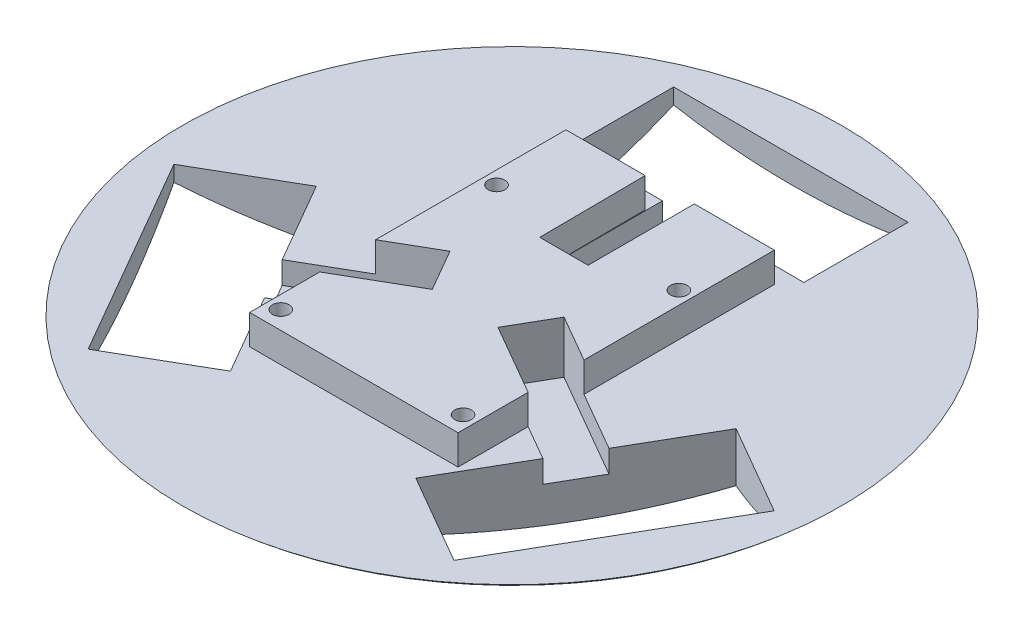
SolidWorks part; units mm, degrees
ref_plane "Front Plane" through (0, 0, 0) normal (0, 0, 1) x (1, 0, 0)
ref_plane "Top Plane" through (0, 0, 0) normal (0, 1, 0) x (1, 0, 0)
ref_plane "Right Plane" through (0, 0, 0) normal (1, 0, 0) x (0, 0, -1)
sketch "Sketch2" plane through (0, 0, 0) normal (0, 1, 0) x (1, 0, 0)
  line L0 (0, -68.0098) -> (0, 65.7503) construction
  line L1 (-31.5, 74.9495) -> (31.5, 74.9495)
  line L2 (-31.5, 74.9495) -> (-31.5, 46.9495)
  line L3 (-31.5, 46.9495) -> (31.5, 46.9495)
  line L4 (31.5, 74.9495) -> (31.5, 46.9495)
  line L5 (-31.5, 74.9495) -> (31.5, 46.9495) construction
  line L6 (-31.5, 46.9495) -> (31.5, 74.9495) construction
  line L7 (-70.2148, 0) -> (95.7201, 0) construction
  line L8 (0, 0) -> (-72.5813, -41.9048) construction
  line L9 (0, 0) -> (72.5813, -41.9048) construction
  line L10 (80.6581, -10.1949) -> (49.1581, -64.7545)
  line L11 (56.4094, 3.8051) -> (24.9094, -50.7545)
  line L12 (80.6581, -10.1949) -> (56.4094, 3.8051)
  line L13 (49.1581, -64.7545) -> (24.9094, -50.7545)
  line L14 (-49.1581, -64.7545) -> (-80.6581, -10.1949)
  line L15 (-24.9094, -50.7545) -> (-56.4094, 3.8051)
  line L16 (-49.1581, -64.7545) -> (-24.9094, -50.7545)
  line L17 (-80.6581, -10.1949) -> (-56.4094, 3.8051)
  line L18 (-6.5, -8.0505) -> (6.5, 46.9495) construction
  line L19 (-6.5, 46.9495) -> (6.5, 46.9495)
  line L20 (-6.5, 46.9495) -> (-6.5, -8.0505)
  line L21 (-6.5, -8.0505) -> (6.5, -8.0505)
  line L22 (6.5, 46.9495) -> (6.5, -8.0505)
  line L23 (-6.5, 46.9495) -> (6.5, -8.0505) construction
  line L24 (31.4023, -15.1408) -> (6.5, -0.7634)
  line L25 (-6.1216, -8.0505) -> (0, 2.5524)
  line L26 (24.9023, -26.3991) -> (0, -12.0218)
  line L27 (-25.0514, -26.4852) -> (0, -12.0218)
  line L28 (0, 2.5524) -> (6.1216, -8.0505)
  line L29 (-33.4324, -16.3129) -> (-6.5, -0.7634)
  circle A2 centre (0, 0) radius 16 construction
  point P3 (0, 19.4495)
  point P4 (0, 46.9495)
  point P6 (0, 60.9495)
  point P13 (0, 0)
  point P33 (0, 0)
  point P41 (0, -4.5162)
  dimension "D1" = 55
  dimension "D2" = 13
  dimension "D3" = 32
  dimension "D5" = 63
  dimension "D6" = 120
  dimension "D7" = 28
  dimension "D8" = 3
  dimension "D4" = 3
sketch "Sketch3" plane through (0, 0, 0) normal (1, 0, 0) x (0, 0, -1)
  line L0 (0, 83.7838) -> (0, -101.0811) construction
  line L1 (-115.9459, 0) -> (127.2973, 0) construction
  line L5 (0, 20) -> (0, 0)
  line L6 (88.569, 20) -> (0, 20)
  arc A3 (84.754, 17.3868) -> (0, 0) centre (7.3808, 179.2865) cw
  arc A4 (84.754, 17.3868) -> (88.569, 20) centre (78.286, 30.9207) ccw
  point P13 (90, 5.0684)
  dimension "D5" = 179.4384
  dimension "D1" = 15
  dimension "D2" = 20
  dimension "D3" = 20
  dimension "D4" = 90
revolve "Revolve1" add sketch "Sketch3" angle 360 about L5
extrude "Cut-Extrude1" cut sketch "Sketch2" along normal blind 40 contours L3 L4 L1 L2 | L15 L17 L14 L16 | L11 L13 L10 L12
sketch "Sketch4" plane through (0, 20, 0) normal (0, 1, 0) x (1, 0, 0)
  line L1 (-6.5, 46.9495) -> (6.5, 46.9495)
  line L2 (-6.5, 46.9495) -> (-6.5, 13.9495)
  line L3 (-6.5, 13.9495) -> (6.5, 13.9495)
  line L4 (6.5, 46.9495) -> (6.5, 13.9495)
  line L5 (-6.5, 46.9495) -> (6.5, 13.9495) construction
  line L6 (-6.5, 13.9495) -> (6.5, 46.9495) construction
  line L7 (43.9094, -17.8456) -> (37.4094, -29.1039)
  line L8 (-56.4094, 3.8051) -> (-24.9094, -50.7545) construction
  line L9 (-31.5, 46.9495) -> (31.5, 46.9495) construction
  line L10 (56.4094, 3.8051) -> (24.9094, -50.7545) construction
  line L26 (43.9094, -17.8456) -> (15.3306, -1.3456)
  line L27 (37.4094, -29.1039) -> (8.8306, -12.6039)
  line L28 (15.3306, -1.3456) -> (8.8306, -12.6039)
  line L29 (-37.4094, -29.1039) -> (-43.9094, -17.8456)
  line L30 (-37.4094, -29.1039) -> (-8.8306, -12.6039)
  line L31 (-43.9094, -17.8456) -> (-15.3306, -1.3456)
  line L32 (-8.8306, -12.6039) -> (-15.3306, -1.3456)
  line L33 (49.1581, -64.7545) -> (41.827, -60.5219)
  line L34 (49.1581, -64.7545) -> (24.9094, -50.7545) construction
  line L35 (49.1581, -64.7545) -> (80.6581, -10.1949)
  line L36 (80.6581, -10.1949) -> (73.327, -5.9623)
  line L37 (80.6581, -10.1949) -> (56.4094, 3.8051) construction
  circle A0 centre (0, 0) radius 88.569 construction
  circle A1 centre (0, 0) radius 73.569 construction
  arc A2 (41.827, -60.5219) -> (73.327, -5.9623) centre (0, 0) ccw
  circle A3 centre (0, 0) radius 81.2999
  point P0 (0, 30.4495)
  point P5 (0, 46.9495)
  point P22 (0, 0)
  point P23 (0, 4.0327)
  point P32 (-2.3282, 4.0326)
  line M8 (-56.4094, 3.8051) -> (-24.9094, -50.7545)
  line M13 (24.9094, -50.7545) -> (56.4094, 3.8051)
  line M17 (31.5, 46.9495) -> (-31.5, 46.9495)
  dimension "D4" = 177.1379
  dimension "D5" = 147.1379
  dimension "D6" = 162.5998
  dimension "D1" = 13
  dimension "D2" = 33
  dimension "D3" = 15
extrude "Cut-Extrude2" cut sketch "Sketch4" against normal blind 6 contours L4 L2 L3 M17 | L30 L32 L31 M8 | L26 L28 L27 M13 region at (0, 20, -30.4495) region at (26.37, 20, 15.2247) region at (-26.37, 20, 15.2247)
sketch "Sketch5" plane through (0, 20, 0) normal (0, 1, 0) x (1, 0, 0)
  line L0 (-28, -23.6714) -> (-8.8306, -12.6039)
  line L1 (-28, 42.5) -> (-6.7113, 42.5)
  line L2 (-28, 42.5) -> (-28, -8.6603)
  line L3 (-28, -42.5) -> (28, -42.5)
  line L4 (28, 42.5) -> (28, -8.6603)
  line L5 (-28, 42.5) -> (28, -42.5) construction
  line L6 (-28, -42.5) -> (28, 42.5) construction
  line L7 (-37.4094, -29.1039) -> (-8.8306, -12.6039) construction
  line L8 (-8.8306, -12.6039) -> (-15.3306, -1.3456)
  line L9 (-15.3306, -1.3456) -> (-28, -8.6603)
  line L10 (-43.9094, -17.8456) -> (-15.3306, -1.3456) construction
  line L11 (28, -23.6714) -> (8.8306, -12.6039)
  line L12 (37.4094, -29.1039) -> (8.8306, -12.6039) construction
  line L13 (8.8306, -12.6039) -> (15.3306, -1.3456)
  line L14 (15.3306, -1.3456) -> (28, -8.6603)
  line L15 (-6.7113, 42.5) -> (-6.5, 13.9495)
  line L16 (-6.5, 13.9495) -> (6.5, 13.9495)
  line L17 (6.5, 13.9495) -> (6.5, 42.5)
  line L18 (6.5, 46.9495) -> (6.5, 13.9495) construction
  line L19 (6.5, 46.9495) -> (6.5, 13.9495) construction
  line L20 (-28, -23.6714) -> (-28, -42.5)
  line L21 (28, -23.6714) -> (28, -42.5)
  line L22 (6.5, 42.5) -> (28, 42.5)
  line L23 (0, 13.9495) -> (0, -42.8187) construction
  line L24 (-28, -8.6603) -> (28, -8.6603) construction
  circle A0 centre (-24.5, -37.6603) radius 2.25
  circle A1 centre (24.5, -37.6603) radius 2.25
  circle A2 centre (24.5, 20.3397) radius 2.25
  circle A3 centre (-24.5, 20.3397) radius 2.25
  point P0 (0, 0)
  dimension "D3" = 4.5
  dimension "D1" = 56
  dimension "D2" = 85
  dimension "D4" = 49
  dimension "D5" = 58
extrude "Boss-Extrude1" add sketch "Sketch5" along normal blind 8
